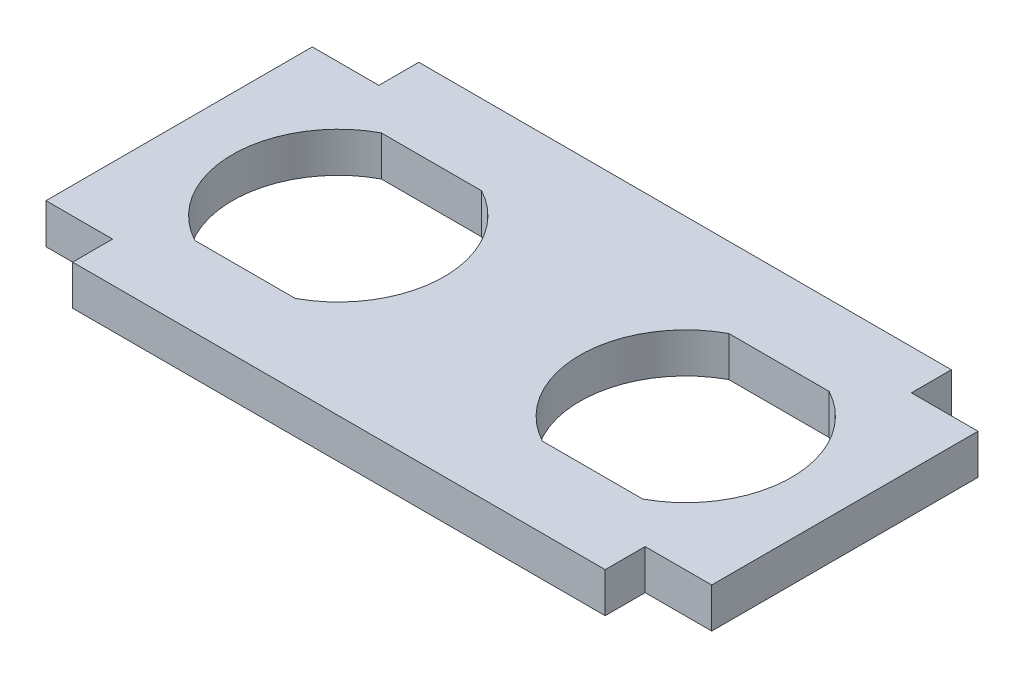
SolidWorks part; units mm, degrees
ref_plane "前视基准面" through (0, 0, 0) normal (0, 0, 1) x (1, 0, 0)
ref_plane "上视基准面" through (0, 0, 0) normal (0, 1, 0) x (1, 0, 0)
ref_plane "右视基准面" through (0, 0, 0) normal (1, 0, 0) x (0, 0, -1)
other "Configuration Table"
sketch "草图1" plane through (0, 0, 0) normal (0, 1, 0) x (1, 0, 0)
  line L1 (-25, -10) -> (25, -10)
  line L2 (-25, -10) -> (-25, 10)
  line L3 (-25, 10) -> (25, 10)
  line L4 (25, -10) -> (25, 10)
  line L5 (-25, -10) -> (25, 10) construction
  line L6 (-25, 10) -> (25, -10) construction
  point P0 (0, 0)
  dimension "D1" = 50
  dimension "D2" = 20
extrude "凸台-拉伸1" add sketch "草图1" along normal blind 3
sketch "草图2" plane through (0, 0, 0) normal (0, -1, 0) x (1, 0, 0)
  circle A0 centre (13.05, 0) radius 7.95
  circle A1 centre (-13.05, 0) radius 7.95
extrude "切除-拉伸1" cut sketch "草图2" against normal blind 10
sketch "草图3" plane through (0, 0, 0) normal (0, -1, 0) x (1, 0, 0)
  line L0 (25, -10) -> (-25, -10) construction
  line L1 (20, -7) -> (-20, -7)
  line L2 (20, -7) -> (20, -13)
  line L3 (20, -13) -> (-20, -13)
  line L4 (-20, -7) -> (-20, -13)
  line L5 (20, -7) -> (-20, -13) construction
  line L6 (20, -13) -> (-20, -7) construction
  line L7 (23.2079, -13) -> (-62.65, -13) construction
  line L8 (-25, 10) -> (25, 10) construction
  line L9 (20, 7) -> (-20, 7)
  line L10 (20, 7) -> (20, 13)
  line L11 (20, 13) -> (-20, 13)
  line L12 (-20, 7) -> (-20, 13)
  line L13 (20, 7) -> (-20, 13) construction
  line L14 (20, 13) -> (-20, 7) construction
  line L15 (23.2079, 13) -> (-62.65, 13) construction
  point P0 (0, -10)
  point P9 (0, 10)
  dimension "D1" = 40
  dimension "D2" = 40
extrude "凸台-拉伸2" add sketch "草图3" against normal blind 3
